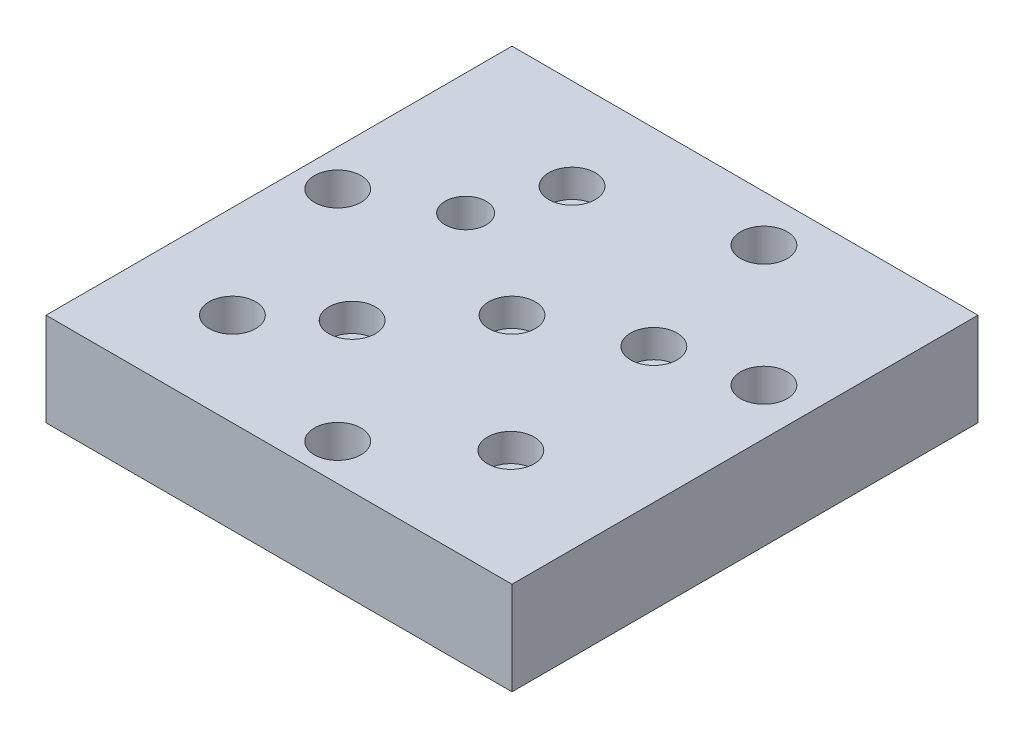
SolidWorks part; units mm, degrees
ref_plane "Front Plane" through (0, 0, 0) normal (0, 0, 1) x (1, 0, 0)
ref_plane "Top Plane" through (0, 0, 0) normal (0, 1, 0) x (1, 0, 0)
ref_plane "Right Plane" through (0, 0, 0) normal (1, 0, 0) x (0, 0, -1)
sketch "Sketch1" plane through (0, 0, 0) normal (0, 1, 0) x (1, 0, 0)
  line L1 (-635, -635) -> (635, -635)
  line L2 (-635, -635) -> (-635, 635)
  line L3 (-635, 635) -> (635, 635)
  line L4 (635, -635) -> (635, 635)
  line L5 (-635, -635) -> (635, 635) construction
  line L6 (-635, 635) -> (635, -635) construction
  circle A0 centre (-381, -381) radius 63.5
  circle A1 centre (-535.4274, 60.3282) radius 63.5
  circle A3 centre (177.9594, 508.5788) radius 63.5
  circle A4 centre (508.5788, 177.9594) radius 63.5
  circle A6 centre (60.3282, -535.4274) radius 63.5
  circle A7 centre (-286.6671, 456.228) radius 63.5 [skipped]
  circle A8 centre (456.228, -286.6671) radius 63.5 [skipped]
  circle A9 centre (-304.2528, 177.9594) radius 55.9428
  point P0 (0, 0)
  point P22 (0, 0)
  dimension "D3" = 127
  dimension "D1" = 1270
  dimension "D2" = 1270
  dimension "D4" = 254
  dimension "D5" = 254
  dimension "D7" = 99.5726
  dimension "D8" = 695.3282
  dimension "D6" = 7
extrude "Boss-Extrude1" add sketch "Sketch1" along normal blind 254
hole_wizard "CBORE for #00 Binding Head Machine Screw1" positions "Sketch2" profile "Sketch3" counterbore size "#00" standard "ANSI Inch" end condition through all
sketch "Sketch2" plane through (0, 254, 0) normal (0, 1, 0) x (1, 0, 0)
  point P0 (0, 0)
  point P4 (-205.8359, -229.8587)
  point P5 (-222.6372, 386.2799)
  point P7 (317.4806, -320.6662)
  point P9 (267.1101, 119.5008)
sketch "Sketch3" plane through (0, 254, 0) normal (1, 0, 0) x (0, 0, 1)
  line L0 (0, 0) -> (0, 254)
  line L1 (0, 254) -> (38.1, 254)
  line L3 (38.1, 254) -> (38.1, 76.2)
  line L4 (38.1, 76.2) -> (63.5, 76.2)
  line L5 (63.5, 76.2) -> (63.5, 0)
  line L7 (63.5, 0) -> (0, 0)
  line L11 (0, -6.35) -> (0, 107.95) construction
  dimension "Thru Hole Dia." = 76.2
  dimension "Thru Hole Depth" = 254
  dimension "C'Bore Dia." = 127
  dimension "C'Bore Depth" = 76.2
